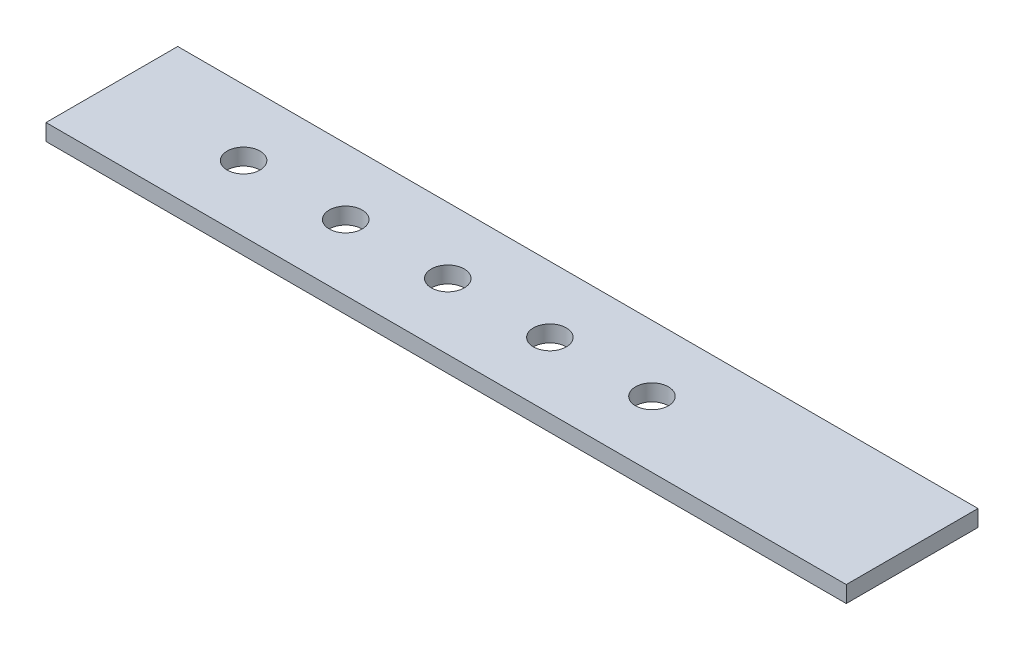
SolidWorks part; units mm, degrees
material "Birch Ply"
ref_plane "Front Plane" through (0, 0, 0) normal (0, 0, 1) x (1, 0, 0)
ref_plane "Top Plane" through (0, 0, 0) normal (0, 1, 0) x (1, 0, 0)
ref_plane "Right Plane" through (0, 0, 0) normal (1, 0, 0) x (0, 0, -1)
sketch "Sketch1" plane through (0, 0, 0) normal (0, 1, 0) x (1, 0, 0)
  line L0 (-154.305, 0) -> (0, 0) construction
  line L1 (-154.305, 12.7) -> (0, 12.7)
  line L2 (-154.305, 12.7) -> (-154.305, -12.7)
  line L3 (-154.305, -12.7) -> (0, -12.7)
  line L4 (0, 12.7) -> (0, -12.7)
  circle A0 centre (-109.22, 0) radius 3.175
  circle A1 centre (-89.535, 0) radius 3.175
  circle A2 centre (-69.85, 0) radius 3.175
  circle A3 centre (-128.905, 0) radius 3.175
  circle A4 centre (-50.165, 0) radius 3.175
  dimension "D4" = 6.35
  dimension "D5" = 6.35
  dimension "D6" = 6.35
  dimension "D3" = 6.35
  dimension "D9" = 6.35
  dimension "D2" = 25.4
  dimension "D7" = 19.685
  dimension "D8" = 19.685
  dimension "D10" = 19.685
  dimension "D11" = 19.685
  dimension "D12" = 69.85
  dimension "D13" = 25.4
extrude "Boss-Extrude1" add sketch "Sketch1" along normal blind 3.175
equation "\"D4@Sketch1\"=\"D3@Sketch1\""
equation "\"D5@Sketch1\"=\"D3@Sketch1\""
equation "\"D6@Sketch1\"=\"D3@Sketch1\""
equation "\"D9@Sketch1\"=\"D3@Sketch1\""
equation "\"D7@Sketch1\"=\"D10@Sketch1\""
equation "\"D8@Sketch1\"=\"D10@Sketch1\""
equation "\"D11@Sketch1\"=\"D10@Sketch1\""
equation "\"D10@Sketch1\"=(0.75+0.8)/2"
